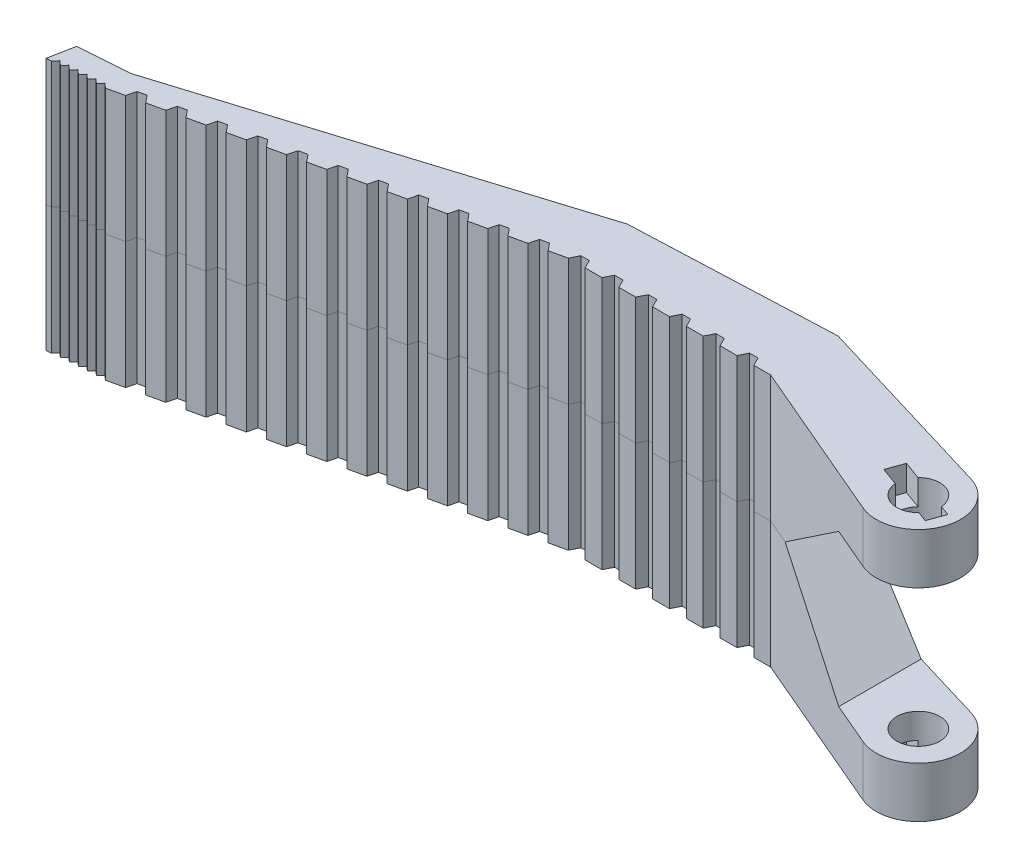
SolidWorks part; units mm, degrees
ref_plane "前视基准面" through (0, 0, 0) normal (0, 0, 1) x (1, 0, 0)
ref_plane "上视基准面" through (0, 0, 0) normal (0, 1, 0) x (1, 0, 0)
ref_plane "右视基准面" through (0, 0, 0) normal (1, 0, 0) x (0, 0, -1)
other "Configuration Table"
ref_axis "基准轴1" through (0, -20.495, 0) along (0, 1, 0)
sketch "草图1" plane through (0, 0, 0) normal (0, 1, 0) x (1, 0, 0)
  line L10 (0, 0) -> (0, -6.4) construction
  line L11 (0, -6.4) -> (-90, -6.4) construction
  line L27 (-1.9651, -4.5977) -> (-21.0954, 3.5788)
  line L29 (-45.0954, 3.5788) -> (-90, -6.4) construction
  line L31 (-90, -3.3924) -> (-45.0954, 10.5788)
  line L32 (-45.0954, 10.5788) -> (-21.0954, 11.5788)
  line L33 (-21.0954, 11.5788) -> (1.4426, 4.7874)
  line L34 (-87.7765, -4.8815) -> (-86.8003, -4.6646)
  line L35 (-86.8003, -4.6646) -> (-86.0953, -5.5323)
  line L36 (-87.7765, -4.8815) -> (-88.0476, -5.9661)
  line L37 (-87.2884, -4.773) -> (-87.0714, -5.7492) construction
  line L38 (-86.0953, -5.5323) -> (-84.1429, -5.0984)
  line L39 (-88.0476, -5.9661) -> (-90, -6.4)
  line L40 (-83.8717, -4.0138) -> (-84.1429, -5.0984)
  line L41 (-83.8717, -4.0138) -> (-82.8955, -3.7968)
  line L42 (-82.8955, -3.7968) -> (-82.1905, -4.6646)
  line L43 (-82.1905, -4.6646) -> (-80.2381, -4.2307)
  line L44 (-79.967, -3.146) -> (-80.2381, -4.2307)
  line L45 (-79.967, -3.146) -> (-78.9908, -2.9291)
  line L46 (-78.9908, -2.9291) -> (-78.2858, -3.7968)
  line L47 (-78.2858, -3.7968) -> (-76.3334, -3.363)
  line L48 (-76.0622, -2.2783) -> (-76.3334, -3.363)
  line L49 (-76.0622, -2.2783) -> (-75.086, -2.0614)
  line L50 (-75.086, -2.0614) -> (-74.381, -2.9291)
  line L51 (-74.381, -2.9291) -> (-72.4286, -2.4953)
  line L52 (-72.1575, -1.4106) -> (-72.4286, -2.4953)
  line L53 (-72.1575, -1.4106) -> (-71.1813, -1.1937)
  line L54 (-71.1813, -1.1937) -> (-70.4763, -2.0614)
  line L55 (-70.4763, -2.0614) -> (-68.5239, -1.6275)
  line L56 (-68.2527, -0.5429) -> (-68.5239, -1.6275)
  line L57 (-68.2527, -0.5429) -> (-67.2765, -0.3259)
  line L58 (-67.2765, -0.3259) -> (-66.5715, -1.1937)
  line L59 (-66.5715, -1.1937) -> (-64.6191, -0.7598)
  line L60 (-64.348, 0.3248) -> (-64.6191, -0.7598)
  line L61 (-64.348, 0.3248) -> (-63.3718, 0.5418)
  line L62 (-63.3718, 0.5418) -> (-62.6668, -0.3259)
  line L63 (-62.6668, -0.3259) -> (-60.7144, 0.1079)
  line L64 (-60.4432, 1.1926) -> (-60.7144, 0.1079)
  line L65 (-60.4432, 1.1926) -> (-59.467, 1.4095)
  line L66 (-59.467, 1.4095) -> (-58.762, 0.5418)
  line L67 (-58.762, 0.5418) -> (-56.8096, 0.9756)
  line L68 (-56.5385, 2.0603) -> (-56.8096, 0.9756)
  line L69 (-56.5385, 2.0603) -> (-55.5623, 2.2772)
  line L70 (-55.5623, 2.2772) -> (-54.8573, 1.4095)
  line L71 (-54.8573, 1.4095) -> (-52.9049, 1.8434)
  line L72 (-52.6337, 2.928) -> (-52.9049, 1.8434)
  line L73 (-52.6337, 2.928) -> (-51.6575, 3.1449)
  line L74 (-51.6575, 3.1449) -> (-50.9525, 2.2772)
  line L75 (-50.9525, 2.2772) -> (-49.0001, 2.7111)
  line L76 (-48.729, 3.7957) -> (-49.0001, 2.7111)
  line L77 (-48.729, 3.7957) -> (-47.7528, 4.0127)
  line L78 (-47.7528, 4.0127) -> (-47.0478, 3.1449)
  line L79 (-47.0478, 3.1449) -> (-45.0954, 3.5788)
  line L80 (-43.0954, 3.5788) -> (-41.0954, 3.5788)
  line L81 (-45.0954, 3.5788) -> (-44.5954, 4.5788)
  line L82 (-44.5954, 4.5788) -> (-43.5954, 4.5788)
  line L83 (-43.5954, 4.5788) -> (-43.0954, 3.5788)
  line L84 (-45.0954, 3.5788) -> (-43.0954, 3.5788) construction
  line L85 (-23.3489, 3.5788) -> (-29.0874, 3.5788) construction
  line L86 (-41.0954, 3.5788) -> (-40.5954, 4.5788)
  line L87 (-40.5954, 4.5788) -> (-39.5954, 4.5788)
  line L88 (-39.5954, 4.5788) -> (-39.0954, 3.5788)
  line L89 (-39.0954, 3.5788) -> (-37.0954, 3.5788)
  line L90 (-41.0954, 3.5788) -> (-39.0954, 3.5788) construction
  line L91 (-37.0954, 3.5788) -> (-36.5954, 4.5788)
  line L92 (-36.5954, 4.5788) -> (-35.5954, 4.5788)
  line L93 (-35.5954, 4.5788) -> (-35.0954, 3.5788)
  line L94 (-35.0954, 3.5788) -> (-33.0954, 3.5788)
  line L95 (-37.0954, 3.5788) -> (-35.0954, 3.5788) construction
  line L96 (-33.0954, 3.5788) -> (-32.5954, 4.5788)
  line L97 (-32.5954, 4.5788) -> (-31.5954, 4.5788)
  line L98 (-31.5954, 4.5788) -> (-31.0954, 3.5788)
  line L99 (-31.0954, 3.5788) -> (-29.0954, 3.5788)
  line L100 (-33.0954, 3.5788) -> (-31.0954, 3.5788) construction
  line L101 (-29.0954, 3.5788) -> (-28.5954, 4.5788)
  line L102 (-28.5954, 4.5788) -> (-27.5954, 4.5788)
  line L103 (-27.5954, 4.5788) -> (-27.0954, 3.5788)
  line L104 (-27.0954, 3.5788) -> (-25.0954, 3.5788)
  line L105 (-29.0954, 3.5788) -> (-27.0954, 3.5788) construction
  line L106 (-25.0954, 3.5788) -> (-24.5954, 4.5788)
  line L107 (-24.5954, 4.5788) -> (-23.5954, 4.5788)
  line L108 (-23.5954, 4.5788) -> (-23.0954, 3.5788)
  line L109 (-23.0954, 3.5788) -> (-21.0954, 3.5788)
  line L110 (-25.0954, 3.5788) -> (-23.0954, 3.5788) construction
  line L111 (-21.0954, 11.5788) -> (-21.0954, 3.5788) construction
  line L112 (-90, -6.4) -> (0, 0) construction
  line L114 (-96.5834, -6.8682) -> (-95.9943, -3.8187)
  line L115 (-95.9943, -3.8187) -> (-90, -3.3924)
  line L116 (-96.5834, -6.8682) -> (-95.9849, -6.8256)
  line L117 (-91.5317, -6.0077) -> (-91.995, -6.5419)
  line L118 (-90.9975, -6.4709) -> (-91.5317, -6.0077)
  line L119 (-92.5292, -6.0786) -> (-92.9924, -6.6128)
  line L120 (-96.5834, -6.8682) -> (-90, -6.4) construction
  line L121 (-90, -6.4) -> (-90.5342, -5.9367)
  line L122 (-90.5342, -5.9367) -> (-90.9975, -6.4709)
  line L123 (-90.5342, -5.9367) -> (-90.4933, -6.5115) construction
  line L124 (-91.995, -6.5419) -> (-92.5292, -6.0786)
  line L125 (-93.5267, -6.1495) -> (-93.9899, -6.6837)
  line L126 (-92.9924, -6.6128) -> (-93.5267, -6.1495)
  line L127 (-94.5241, -6.2205) -> (-94.9874, -6.7547)
  line L128 (-93.9899, -6.6837) -> (-94.5241, -6.2205)
  line L129 (-95.5216, -6.2914) -> (-95.9849, -6.8256)
  line L130 (-94.9874, -6.7547) -> (-95.5216, -6.2914)
  arc A0 (1.4426, 4.7874) -> (-1.9651, -4.5977) centre (0, 0) cw
  point P38 (-44.0954, 4.5788)
  point P43 (-44.0954, 3.5788)
  dimension "D4" = 7
  dimension "D3" = 5
  dimension "D1" = 6.4
  dimension "D5" = 6
  dimension "D6" = 2
  dimension "D7" = 8
  dimension "D8" = 2
  dimension "D9" = 0.6
  dimension "D10" = 1
  dimension "D11" = 1
  dimension "D12" = 1
  dimension "D13" = 2
  dimension "D14" = 2
  dimension "D15" = 2
  dimension "D17" = 1
  dimension "D18" = 1
  dimension "D19" = 6
  dimension "D20" = 75
  dimension "D21" = 3
  dimension "D16" = 11
extrude "凸台-拉伸2" add sketch "草图1" along normal blind 15 and the other way blind 15
sketch "草图10" plane through (0, 0, 0) normal (0, 0, 1) x (1, 0, 0)
  line L0 (5, 9) -> (-7, 9)
  line L1 (5, -15) -> (5, 15) construction
  line L4 (55, 0) -> (-55, 0) construction
  line L8 (5, 15) -> (-1.9651, 15) construction
  line L12 (-18.0954, 0) -> (19.8896, 0) construction
  line L14 (-18.0954, 0) -> (-7, 9)
  line L15 (5, 9) -> (5, -9)
  line L16 (5, -15) -> (5, 15) construction
  line L17 (-18.0954, 0) -> (-7, -9)
  line L18 (5, -9) -> (-7, -9)
  line L19 (-21.0954, -15) -> (-21.0954, 15) construction
  point P18 (5, 0)
  point P26 (5, 0)
  dimension "D1" = 6
  dimension "D2" = 3
  dimension "D3" = 12
extrude "切除-拉伸7" cut sketch "草图10" against normal through all and the other way through all
sketch "草图5" plane through (0, -15, 0) normal (0, -1, 0) x (1, 0, 0)
  circle A0 centre (0, 0) radius 2.55
  dimension "D1" = 5.1
extrude "切除-拉伸2" cut sketch "草图5" against normal through all
sketch "草图8" plane through (0, -15, 0) normal (0, -1, 0) x (1, 0, 0)
  line L0 (0, 0) -> (-4.3238, -1.57) construction
  line L1 (1.4426, -4.7874) -> (-21.0954, -11.5788) construction
  line L2 (-21.0954, -3.5788) -> (-1.9651, 4.5977) construction
  line L3 (-4.6822, -0.583) -> (-3.9654, -2.5569)
  line L7 (-4.6822, -0.583) -> (3.0255, 2.2156)
  line L8 (-3.9654, -2.5569) -> (3.7422, 0.2417)
  line L9 (0, 0) -> (3.3838, 1.2287) construction
  line L10 (3.7422, 0.2417) -> (3.0255, 2.2156)
  point P9 (-4.3238, -1.57)
  point P10 (3.3838, 1.2287)
  dimension "D1" = 4.6
  dimension "D2" = 2.1
  dimension "D3" = 3.6
extrude "切除-拉伸5" cut sketch "草图8" against normal blind 3
mirror "镜向1" about plane through (0, 0, 0) normal (0, 1, 0) of "切除-拉伸5"
sketch "草图12" plane through (0, 0, 0) normal (0, 0, 1) x (1, 0, 0)
  line L0 (-97.3133, 0) -> (15.6219, 0)
  line L1 (10.1458, 0) -> (-10.1458, 0) construction
split "分割1" trim tools "草图12" bodies to split 123 resulting bodies 124 125
